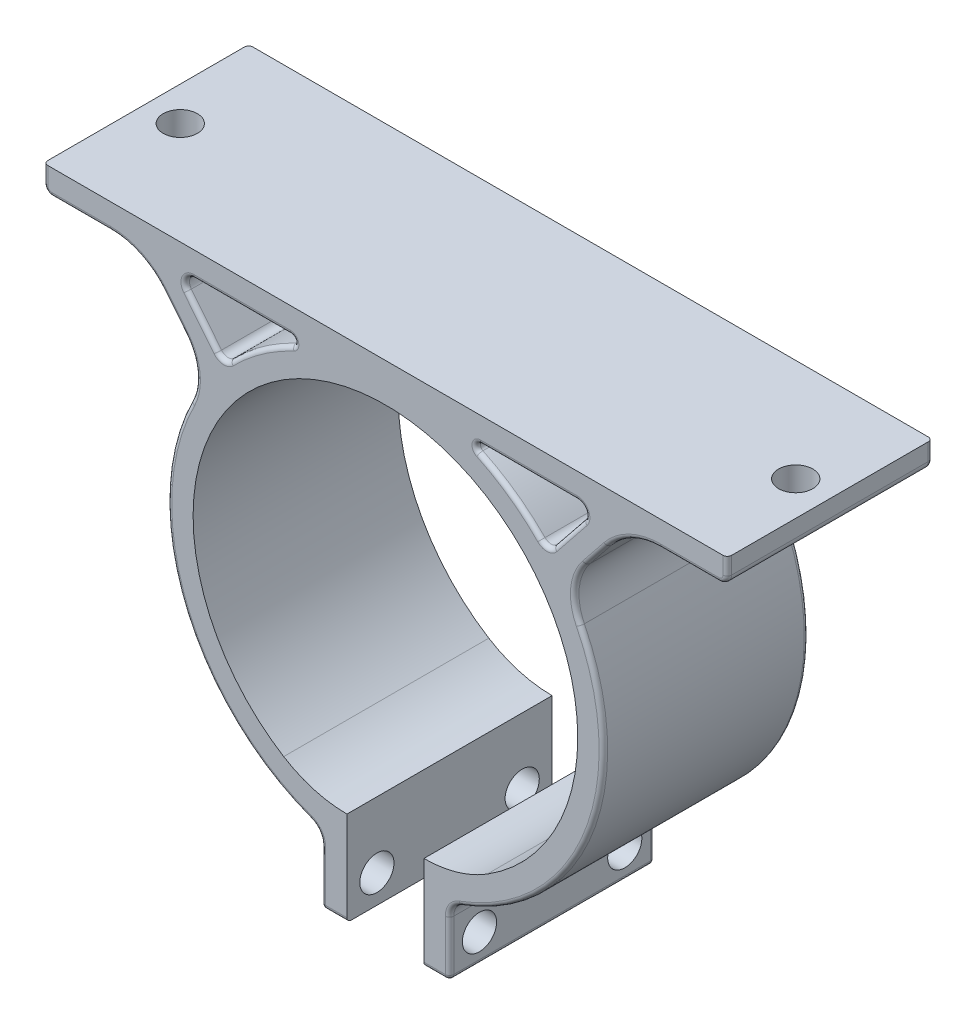
SolidWorks part; units mm, degrees
ref_plane "Ebene vorne" through (0, 0, 0) normal (0, 0, 1) x (1, 0, 0)
ref_plane "Ebene oben" through (0, 0, 0) normal (0, 1, 0) x (1, 0, 0)
ref_plane "Ebene rechts" through (0, 0, 0) normal (1, 0, 0) x (0, 0, -1)
ref_plane "Ebene1" through (0, 0, 10) normal (0, 0, 1) x (1, 0, 0)
ref_plane "Ebene4" through (0, 0, 0) normal (1, 0, 0) x (0, 0, -1)
ref_plane "Ebene5" through (0, 0, 0) normal (0, 1, 0) x (1, 0, 0)
sketch "Skizze1" plane through (0, 0, 10) normal (0, 0, 1) x (1, 0, 0)
  circle A0 centre (0, 0) radius 22.5
  circle A1 centre (0, 0) radius 25.5
extrude "Aufsatz-Linear austragen1" add sketch "Skizze1" along normal blind 24
sketch "Skizze2" plane through (0, 0, 10) normal (0, 0, 1) x (1, 0, 0)
  line L0 (0, -55) -> (0, 55) construction
  line L8 (7.5, -18.9352) -> (-7.5, -18.9352)
  line L9 (7.5, -18.9352) -> (7.5, -28.9352)
  line L10 (7.5, -28.9352) -> (-7.5, -28.9352)
  line L11 (-7.5, -18.9352) -> (-7.5, -28.9352)
  line L12 (7.5, -18.9352) -> (-7.5, -28.9352) construction
  line L13 (7.5, -28.9352) -> (-7.5, -18.9352) construction
  circle A0 centre (0, 0) radius 25.5 construction
  point P0 (0, 25.5)
  point P10 (0, -23.9352)
  dimension "D3" = 15
  dimension "D4" = 10
extrude "Schnitt-Linear austragen3" cut sketch "Skizze2" along normal blind 25
sketch "Skizze5" plane through (0, 0, 10) normal (0, 0, 1) x (1, 0, 0)
  line L1 (40, 27) -> (-40, 27)
  line L2 (40, 27) -> (40, 24)
  line L3 (40, 24) -> (-40, 24)
  line L4 (-40, 27) -> (-40, 24)
  line L5 (40, 27) -> (-40, 24) construction
  line L6 (40, 24) -> (-40, 27) construction
  arc A0 (7.5, -24.3721) -> (-7.5, -24.3721) centre (0, 0) ccw construction
  point P0 (0, 25.5)
  dimension "D1" = 80
  dimension "D2" = 3
extrude "Aufsatz-Linear austragen2" add sketch "Skizze5" along normal blind 24
sketch "Skizze6" plane through (0, 0, 10) normal (0, 0, 1) x (1, 0, 0)
  line L0 (0, -55) -> (0, 55) construction
  line L1 (7.5, -21.2132) -> (4.5, -21.2132)
  line L2 (7.5, -21.2132) -> (7.5, -32.2132)
  line L3 (7.5, -32.2132) -> (4.5, -32.2132)
  line L4 (4.5, -21.2132) -> (4.5, -32.2132)
  line L5 (-7.5, -32.2132) -> (-4.5, -32.2132)
  line L6 (-4.5, -21.2132) -> (-4.5, -32.2132)
  line L7 (-7.5, -21.2132) -> (-4.5, -21.2132)
  line L8 (-7.5, -21.2132) -> (-7.5, -32.2132)
  dimension "D1" = 3
  dimension "D2" = 11
extrude "Aufsatz-Linear austragen3" add sketch "Skizze6" along normal blind 24
sketch "Skizze10" plane through (0, 0, 10) normal (0, 0, 1) x (1, 0, 0)
  line L0 (28.3453, 24) -> (20.8645, 14.6602)
  line L1 (8.6168, 24) -> (40, 24) construction
  line L2 (24.5016, 24) -> (18.9475, 17.0658)
  line L3 (28.3453, 24) -> (24.5016, 24)
  line L4 (0, -55) -> (0, 55) construction
  line L5 (-24.5016, 24) -> (-18.9475, 17.0658)
  line L6 (-28.3453, 24) -> (-24.5016, 24)
  line L7 (-28.3453, 24) -> (-20.8645, 14.6602)
  arc A0 (7.5, -24.3721) -> (8.6168, 24) centre (0, 0) ccw construction
  arc A2 (18.9475, 17.0658) -> (20.8645, 14.6602) centre (20.1783, 16.08) ccw
  arc A3 (-18.9475, 17.0658) -> (-20.8645, 14.6602) centre (-20.1783, 16.08) cw
  dimension "D1" = 3
extrude "Aufsatz-Linear austragen4" add sketch "Skizze10" along normal blind 24
fillet "Verrundung3" radius 6 2 edges at (-20.8645, 14.6602, 22) (20.8645, 14.6602, 22)
fillet "Verrundung4" radius 1 2 edges at (18.9475, 17.0658, 22) (-18.9475, 17.0658, 22)
fillet "Verrundung5" radius 1 2 edges at (-24.5016, 24, 22) (24.5016, 24, 22)
fillet "Verrundung6" radius 0.5 2 edges at (-8.6168, 24, 22) (8.6168, 24, 22)
fillet "Verrundung11" radius 14 2 edges at (-7.5, -21.2132, 22) (7.5, -21.2132, 22)
fillet "Verrundung12" radius 2 2 edges at (-7.5, -24.3721, 22) (7.5, -24.3721, 22)
fillet "Verrundung13" radius 1 2 edges at (-40, 24, 22) (40, 24, 22)
sketch "Skizze11" plane through (0, 27, 0) normal (0, 1, 0) x (1, 0, 0)
  line L0 (-39, -34) -> (-28.3453, -34) construction
  line L1 (0, -55) -> (0, 55) construction
  circle A0 centre (36, -22) radius 2
  circle A1 centre (-36, -22) radius 2
  dimension "D1" = 72
  dimension "D2" = 12
extrude "Schnitt-Linear austragen4" cut sketch "Skizze11" against normal blind 20
sketch "Skizze12" plane through (-7.5, 0, 0) normal (-1, 0, 0) x (0, 0, 1)
  line L0 (10, -25.807) -> (10, -32.2132) construction
  line L1 (34, -25.807) -> (34, -32.2132) construction
  line L2 (34, -32.2132) -> (10, -32.2132) construction
  circle A0 centre (13.5, -28.9132) radius 2
  circle A1 centre (30.5, -28.9132) radius 2
  dimension "D1" = 3.5
  dimension "D2" = 3.5
  dimension "D3" = 3.3
  dimension "D4" = 3.3
extrude "Schnitt-Linear austragen5" cut sketch "Skizze12" against normal blind 22
fillet "Verrundung14" radius 0.5 2 edges at (-7.5, -32.2132, 22) (7.5, -32.2132, 22)
fillet "Verrundung15" radius 8 2 edges at (28.3453, 24, 22) (-28.3453, 24, 22)
fillet "Verrundung16" radius 0.5 44 edges at (7.3536, -32.0668, 34) (-23.7177, -9.3661, 34) (-40, 26, 34) (-39.7071, 24.2929, 34) (-35.5937, 24, 34) (-28.724, 23.2114, 34) (-24.7017, 19.451, 34) (-22.1759, 14.7771, 34) (-7.8596, -24.6628, 34) (-7.5, -28.7601, 34) (-7.3536, -32.0668, 34) (-5.75, -32.2132, 34) (5.75, -32.2132, 34) (7.5, -28.7601, 34) (7.8596, -24.6628, 34) (23.7177, -9.3661, 34) (22.1759, 14.7771, 34) (24.7017, 19.451, 34) (28.724, 23.2114, 34) (35.5937, 24, 34) (39.7071, 24.2929, 34) (40, 26, 34) (40, 26, 10) (39.7071, 24.2929, 10) (35.5937, 24, 10) (28.724, 23.2114, 10) (24.7017, 19.451, 10) (22.1759, 14.7771, 10) (23.7177, -9.3661, 10) (7.8596, -24.6628, 10) (7.5, -28.7601, 10) (7.3536, -32.0668, 10) (5.75, -32.2132, 10) (-5.75, -32.2132, 10) (-7.3536, -32.0668, 10) (-7.5, -28.7601, 10) (-7.8596, -24.6628, 10) (-23.7177, -9.3661, 10) (-22.1759, 14.7771, 10) (-24.7017, 19.451, 10) (-28.724, 23.2114, 10) (-35.5937, 24, 10) (-39.7071, 24.2929, 10) (-40, 26, 10)
fillet "Verrundung17" radius 0.5 24 edges at (-16.7719, 24, 34) (-10.6365, 23.6096, 34) (-23.3208, 23.4329, 34) (-21.4334, 20.1694, 34) (-18.9375, 17.5904, 34) (-14.7692, 20.7875, 34) (23.3208, 23.4329, 34) (16.7719, 24, 34) (10.6365, 23.6096, 34) (14.7692, 20.7875, 34) (18.9375, 17.5904, 34) (21.4334, 20.1694, 34) (-10.6365, 23.6096, 10) (-14.7692, 20.7875, 10) (-18.9375, 17.5904, 10) (-21.4334, 20.1694, 10) (-23.3208, 23.4329, 10) (-16.7719, 24, 10) (14.7692, 20.7875, 10) (18.9375, 17.5904, 10) (21.4334, 20.1694, 10) (23.3208, 23.4329, 10) (16.7719, 24, 10) (10.6365, 23.6096, 10)
